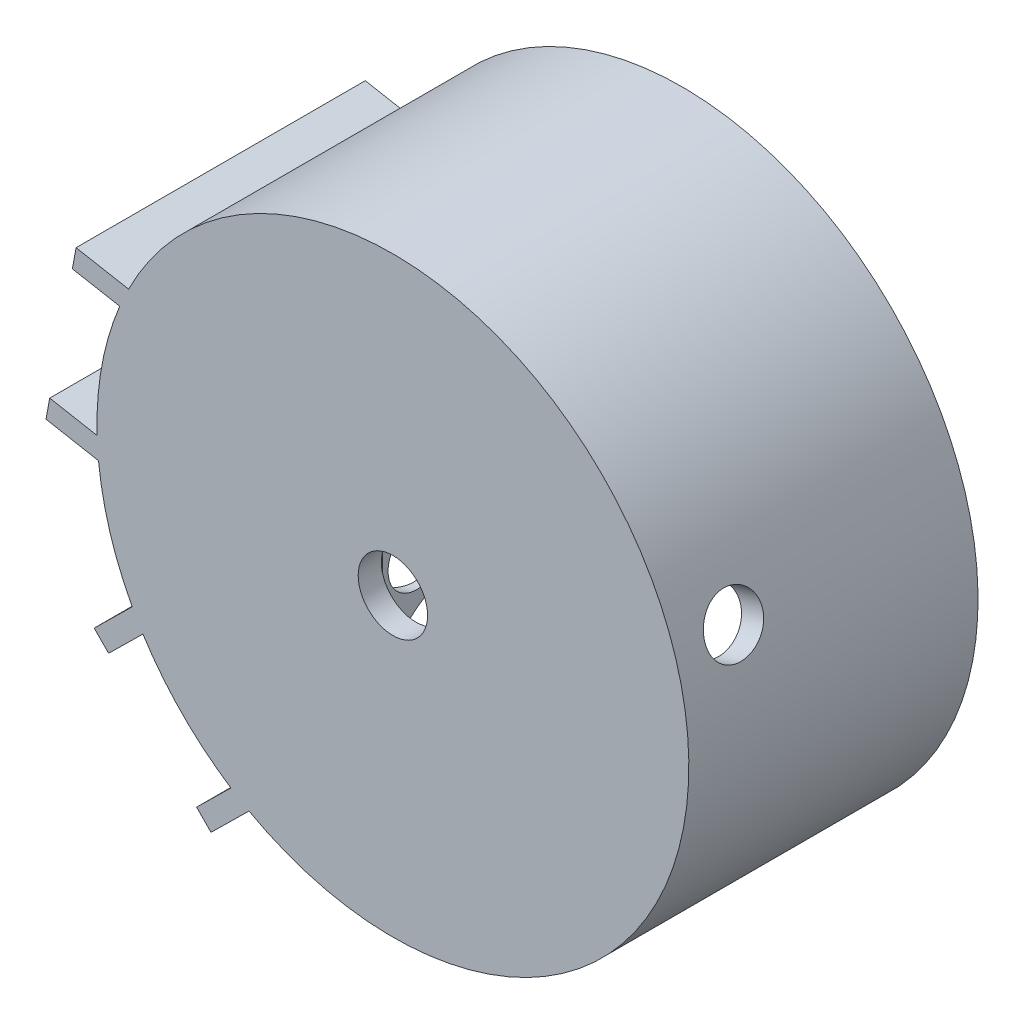
SolidWorks part; units mm, degrees
ref_plane "Front Plane" through (0, 0, 0) normal (0, 0, 1) x (1, 0, 0)
ref_plane "Top Plane" through (0, 0, 0) normal (0, 1, 0) x (1, 0, 0)
ref_plane "Right Plane" through (0, 0, 0) normal (1, 0, 0) x (0, 0, -1)
sketch "Sketch1" plane through (0, 0, 0) normal (0, 0, 1) x (1, 0, 0)
  circle A0 centre (0, 0) radius 14.15
  circle A1 centre (0, 0) radius 1.8
  dimension "D1" = 28.3
  dimension "D2" = 3.6
extrude "Boss-Extrude1" add sketch "Sketch1" along normal blind 1.2
sketch "Sketch3" plane through (0, 0, 1.2) normal (0, 0, 1) x (1, 0, 0)
  circle A0 centre (0, 0) radius 14.15
  circle A1 centre (0, 0) radius 15.35
  circle A2 centre (0, 0) radius 14.15 construction
  dimension "D1" = 1.2
extrude "Boss-Extrude2" add sketch "Sketch3" against normal blind 15
sketch "Sketch5" plane through (0, 0, -13.8) normal (0, 0, -1) x (-1, 0, 0)
  line L0 (2.9228, -7.0326) -> (10.4462, -14.3571)
  line L1 (10.4462, -14.3571) -> (14.6317, -10.058)
  line L2 (14.6317, -10.058) -> (7.1083, -2.7335)
  line L3 (7.1083, -2.7335) -> (2.9228, -7.0326)
  line L4 (7.4302, -1.6708) -> (17.7536, 0.2473)
  line L6 (17.7536, 0.2473) -> (16.6575, 6.1463)
  line L7 (16.6575, 6.1463) -> (6.3342, 4.2282)
  line L8 (6.3342, 4.2282) -> (7.4302, -1.6708)
  circle A1 centre (0, 0) radius 13.5
  circle M3 centre (0, 0) radius 14.15
  circle M4 centre (0, 0) radius 15.35
extrude "Cut-Extrude2" cut sketch "Sketch5" against normal blind 8 contours L7 L4 M4 M3 | L2 L0 M4 M3 region at (-10.4947, -10.2173, -13.8) region at (-14.4005, 2.6756, -13.8)
sketch "Sketch6" plane through (-12.4634, -12.2847, 0) normal (-0.7122, -0.702, 0) x (0, 0, 1)
  line L0 (-13.8, 15.35) -> (-13.8, -15.35) construction
  line L1 (0.5, 3) -> (-24, 3) construction
  line L2 (-13.8, -3.25) -> (8.3607, -3.25)
  line L3 (-13.8, -3.25) -> (-13.8, 3.25)
  line L4 (-13.8, 3.25) -> (8.3607, 3.25)
  line L5 (8.3607, -3.25) -> (8.3607, 3.25)
  line L6 (-13.8, -3.25) -> (8.3607, 3.25) construction
  line L7 (-13.8, 3.25) -> (8.3607, -3.25) construction
  line L9 (-13.8, -4.3148) -> (8.3607, -4.3148)
  line L10 (-13.8, -4.3148) -> (-13.8, 4.3148)
  line L11 (-13.8, 4.3148) -> (8.3607, 4.3148)
  line L12 (8.3607, -4.3148) -> (8.3607, 4.3148)
  line L13 (-13.8, -4.3148) -> (8.3607, 4.3148) construction
  line L14 (-13.8, 4.3148) -> (8.3607, -4.3148) construction
  line L15 (1.2, -15.35) -> (1.2, 15.35) construction
  line L16 (1.2, 4.3148) -> (1.2, -4.3148)
  point P0 (-2.7197, 0)
  point P8 (-2.7197, 0)
  dimension "D1" = 0.25
extrude "Boss-Extrude3" add sketch "Sketch6" against normal up to surface (2.498 mm away) contours L4 L12 L11 L10 | L9 L12 L2 L10 region at (-9.8082, -14.9785, -6.3) region at (-15.1185, -9.591, -6.3) up to face at (-9.658, -2.9258, -9.8)
pattern_circular "CirPattern1" count 2 every 305 about axis through (0, 0, 1.2) along (0, 0, 1) of "Boss-Extrude3"
sketch "Sketch7" plane through (0, 0, 0) normal (0, 0, -1) x (-1, 0, 0)
  circle A0 centre (0, 0) radius 1.75
  circle A1 centre (0, 0) radius 2.75
  dimension "D1" = 1
extrude "Boss-Extrude4" add sketch "Sketch7" along normal blind 4
fillet "Fillet1" radius 4 1 edges at (2.75, 0, 0)
sketch "Sketch8" plane through (0, 0, -4) normal (0, 0, -1) x (-1, 0, 0)
  line L1 (-1.75, 7.8166) -> (1.75, 7.8166)
  line L2 (-1.75, 7.8166) -> (-1.75, -7.8166)
  line L3 (-1.75, -7.8166) -> (1.75, -7.8166)
  line L4 (1.75, 7.8166) -> (1.75, -7.8166)
  line L5 (-1.75, 7.8166) -> (1.75, -7.8166) construction
  line L6 (-1.75, -7.8166) -> (1.75, 7.8166) construction
  point P0 (0, 0)
  dimension "D1" = 3.5
extrude "Cut-Extrude3" cut sketch "Sketch8" against normal up to surface (4 mm away) up to face at (6.75, 0, 0)
sketch "Sketch11" plane through (0, 0, -13.8) normal (0, 0, -1) x (-1, 0, 0)
  line L0 (10.6459, 11.7096) -> (1.7883, -17.1065)
  line L1 (1.7883, -17.1065) -> (-20.7296, -15.1586)
  line L2 (-20.7296, -15.1586) -> (-20.1842, 12.1122)
  line L3 (-20.1842, 12.1122) -> (12.385, 20.7609)
  line L4 (12.385, 20.7609) -> (10.6459, 11.7096)
  line L5 (17.9917, -1.0806) -> (15.4923, -9.2118)
  arc M7 (7.8154, -11.7958) -> (13.0476, 5.4756) centre (0, 0) cw
  arc M13 (13.7086, 6.9064) -> (7.4625, -13.414) centre (0, 0) ccw
extrude "Cut-Extrude5" [suppressed] cut sketch "Sketch11" against normal up to surface (13.8 mm away) contours L0 M13 M7
ref_plane "Plane1" through (-16.742, -5.1462, 0) normal (0.9559, 0.2938, 0) x (0, 0, -1)
sketch "Sketch4" plane through (-17.515, -2.6312, 0) normal (0.9559, 0.2938, 0) x (0.2938, -0.9559, 0)
  line L0 (17.9812, 13.8) -> (-12.7188, 13.8) construction
  circle A0 centre (2.6312, 1.8) radius 1.5
  dimension "D1" = 3
  dimension "D2" = 12
extrude "Cut-Extrude1" cut sketch "Sketch4" along normal blind 37
sketch "Sketch12" plane through (0, 0, -13.8) normal (0, 0, -1) x (-1, 0, 0)
  line L0 (13.5255, -4.1575) -> (0, 0) construction
  line L1 (12.4407, -7.6865) -> (-1.0848, -3.529)
  line L2 (14.6102, -0.6285) -> (1.0848, 3.529)
  circle A0 centre (0, 0) radius 14.15 construction
  arc A1 (12.4407, -7.6865) -> (14.6102, -0.6285) centre (13.5255, -4.1575) ccw
  arc A2 (1.0848, 3.529) -> (-1.0848, -3.529) centre (0, 0) ccw
  circle A3 centre (0, 0) radius 15.35
  circle A4 centre (0, 0) radius 1.75
  point P5 (6.7627, -2.0787)
  arc M8 (14.1437, -0.4234) -> (12.0009, -7.4968) centre (0, 0) cw
  line M9 (12.0009, -7.4968) -> (12.8791, -8.3518)
  arc M14 (13.5203, -7.2681) -> (15.2684, -1.581) centre (0, 0) ccw
extrude "Boss-Extrude6" [suppressed] add sketch "Sketch12" along normal blind 1.4 contours A1 A3 L2 L1 M14 M8 M9 | L2 A2 L1 A4 M9 M8
